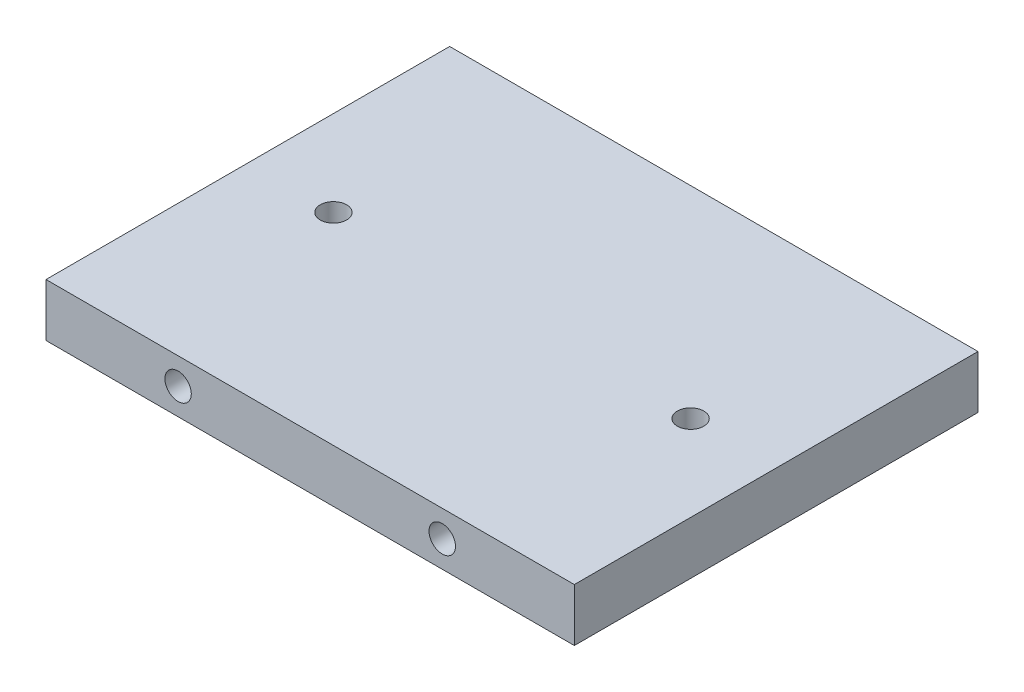
SolidWorks part; units mm, degrees
ref_plane "Front Plane" through (0, 0, 0) normal (0, 0, 1) x (1, 0, 0)
ref_plane "Top Plane" through (0, 0, 0) normal (0, 1, 0) x (1, 0, 0)
ref_plane "Right Plane" through (0, 0, 0) normal (1, 0, 0) x (0, 0, -1)
sketch "Sketch1" plane through (0, 0, 0) normal (0, 1, 0) x (1, 0, 0)
  line L0 (0, 97.028) -> (63.5, 97.028)
  line L1 (63.5, 97.028) -> (63.5, 0)
  line L2 (63.5, 0) -> (-63.5, 0)
  line L3 (-63.5, 0) -> (-63.5, 97.028)
  line L4 (-63.5, 97.028) -> (0, 97.028)
  line L5 (-63.5, 48.514) -> (-42.926, 48.514) construction
  line L6 (-42.926, 48.514) -> (42.926, 48.514) construction
  line L7 (42.926, 48.514) -> (63.5, 48.514) construction
  circle A0 centre (-42.926, 48.514) radius 3.175
  circle A1 centre (42.926, 48.514) radius 3.175
  point P12 (-31.4314, 38.1)
  dimension "D3" = 6.35
  dimension "D1" = 127
  dimension "D2" = 48.514
  dimension "D4" = 85.852
extrude "Boss-Extrude1" add sketch "Sketch1" along normal blind 12.7
sketch "Sketch3" plane through (0, 0, 0) normal (0, 0, 1) x (1, 0, 0)
  line L0 (-78.7739, 6.35) -> (79.2116, 6.35) construction
  line L1 (-63.5, 12.7) -> (-63.5, 0) construction
  line L2 (63.5, 12.7) -> (63.5, 0) construction
  circle A0 centre (-31.75, 6.35) radius 3.175
  circle A1 centre (31.75, 6.35) radius 3.175
  point P6 (0, 0)
  point P11 (0, 0)
  point P12 (-63.5, 6.35)
  dimension "D1" = 6.35
  dimension "D2" = 31.75
  dimension "D3" = 31.75
extrude "Cut-Extrude1" cut sketch "Sketch3" against normal through all
